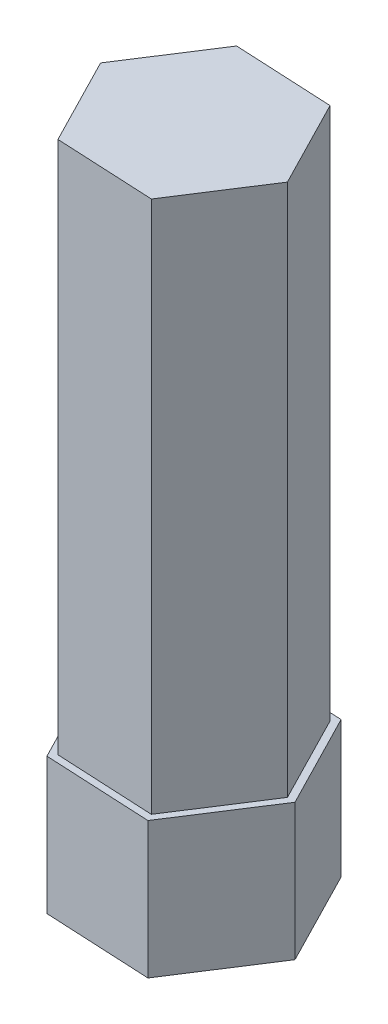
SolidWorks part; units mm, degrees
ref_plane "Front Plane" through (0, 0, 0) normal (0, 0, 1) x (1, 0, 0)
ref_plane "Top Plane" through (0, 0, 0) normal (0, 1, 0) x (1, 0, 0)
ref_plane "Right Plane" through (0, 0, 0) normal (1, 0, 0) x (0, 0, -1)
sketch "Sketch2" plane through (0, 0, 0) normal (0, 1, 0) x (1, 0, 0)
  line L1 (13.1511, 20.3728) -> (-11.0678, 21.5755)
  line L2 (-11.0678, 21.5755) -> (-24.2189, 1.2028)
  line L3 (-24.2189, 1.2028) -> (-13.1511, -20.3728)
  line L4 (-13.1511, -20.3728) -> (11.0678, -21.5755)
  line L5 (11.0678, -21.5755) -> (24.2189, -1.2028)
  line L6 (24.2189, -1.2028) -> (13.1511, 20.3728)
  circle A0 centre (0, 0) radius 21 construction
  dimension "D1" = 42
extrude "Boss-Extrude1" add sketch "Sketch2" along normal blind 131.3
sketch "Sketch3" plane through (0, 0, 0) normal (0, -1, 0) x (1, 0, 0)
  line L0 (-13.1511, 20.3728) -> (11.0678, 21.5755) construction
  line L1 (11.9638, 23.3221) -> (-14.2157, 22.022)
  line L2 (-14.2157, 22.022) -> (-26.1794, -1.3002)
  line L3 (-26.1794, -1.3002) -> (-11.9638, -23.3221)
  line L4 (-11.9638, -23.3221) -> (14.2157, -22.022)
  line L5 (14.2157, -22.022) -> (26.1794, 1.3002)
  line L6 (26.1794, 1.3002) -> (11.9638, 23.3221)
  circle A0 centre (0, 0) radius 22.7 construction
  dimension "D1" = 45.4
extrude "Boss-Extrude2" add sketch "Sketch3" along normal blind 33.6
